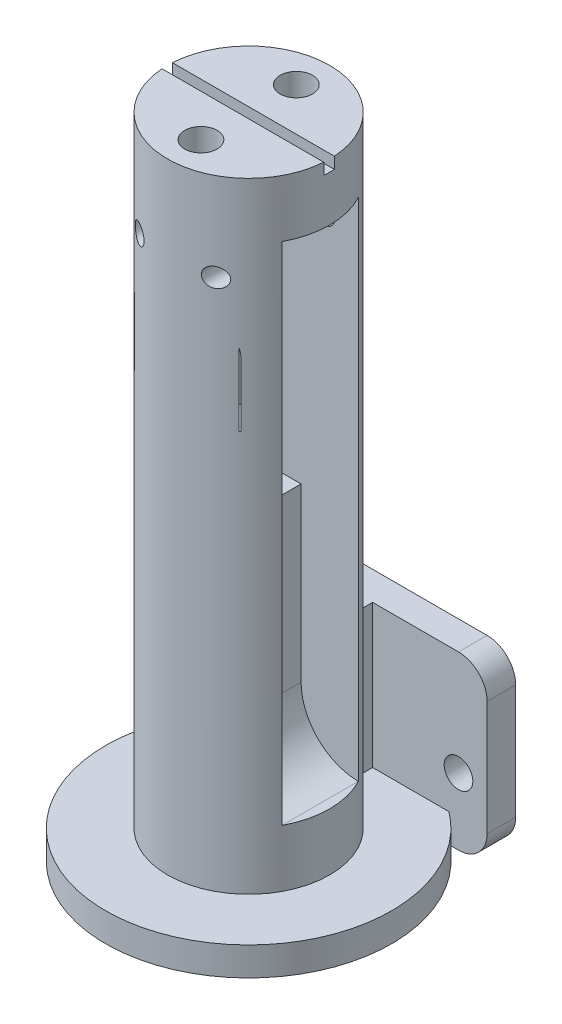
SolidWorks part; units mm, degrees
material "CA"
ref_plane "Alzado" through (0, 0, 0) normal (0, 0, 1) x (1, 0, 0)
ref_plane "Planta" through (0, 0, 0) normal (0, 1, 0) x (1, 0, 0)
ref_plane "Vista lateral" through (0, 0, 0) normal (1, 0, 0) x (0, 0, -1)
sketch "Croquis1" plane through (0, 0, 0) normal (0, 1, 0) x (1, 0, 0)
  circle A0 centre (0, 0) radius 15
  dimension "D1" = 30
extrude "Saliente-Extruir1" add sketch "Croquis1" along normal blind 3
sketch "Croquis2" plane through (0, 3, 0) normal (0, 1, 0) x (1, 0, 0)
  circle A0 centre (0, 0) radius 8.5
  dimension "D1" = 17
extrude "Saliente-Extruir2" add sketch "Croquis2" along normal blind 65
sketch "Croquis3" plane through (0, 0, 0) normal (0, 0, 1) x (1, 0, 0)
  line L0 (8.5, 3) -> (-8.5, 3) construction
  line L1 (-8.5, 62) -> (8.5, 62)
  line L2 (-8.5, 62) -> (-8.5, 9)
  line L3 (-8.5, 9) -> (8.5, 9)
  line L4 (8.5, 62) -> (8.5, 9)
  line L5 (-8.5, 62) -> (8.5, 9) construction
  line L6 (-8.5, 9) -> (8.5, 62) construction
  line L7 (7.5, 68) -> (-7.5, 68) construction
  point P0 (0, 35.5)
  dimension "D1" = 6
  dimension "D2" = 6
  dimension "D3" = 17
  dimension "D4" = 0
extrude "Cortar-Extruir1" cut sketch "Croquis3" against normal blind 4 and the other way blind 4 contours L2 L1 L4 L3
sketch "Croquis4" plane through (0, 0, 0) normal (0, 0, 1) x (1, 0, 0)
  line L0 (7.5, 68) -> (-7.5, 68) construction
  line L1 (0, 68) -> (0, 44.0462) construction
  circle A0 centre (-4, 58.75) radius 1
  circle A1 centre (4, 58.75) radius 1
  dimension "D1" = 2
  dimension "D2" = 4
  dimension "D5" = 9.25
extrude "Cortar-Extruir2" cut sketch "Croquis4" against normal blind 8 and the other way blind 8
sketch "Sketch9" plane through (0, 0, 0) normal (0, 0, 1) x (1, 0, 0)
  line L1 (-15.5683, -0.9904) -> (15.9293, -0.9904)
  line L2 (-15.5683, -0.9904) -> (-15.5683, 65.5246)
  line L3 (-15.5683, 65.5246) -> (15.9293, 65.5246)
  line L4 (15.9293, -0.9904) -> (15.9293, 65.5246)
extrude "Cut-Extrude7" [suppressed] cut sketch "Sketch9" against normal blind 30
sketch "Sketch10" [suppressed] plane through (0, 0, 3) normal (0, 0, -1) x (-1, 0, 0)
  line L0 (0, 63) -> (0, 0) construction
  line L2 (-5.6, 48.5) -> (-5.6, 42)
  line L3 (-5.6, 42) -> (5.6, 42)
  line L4 (5.6, 48.5) -> (5.6, 42)
  line L5 (-7.5, 63) -> (7.5, 63) construction
  line L6 (7.953, 57) -> (-7.953, 57) construction
  arc A3 (-5.6, 48.5) -> (5.6, 48.5) centre (0, 48.5) cw
  dimension "D3" = 15
  dimension "D4" = 5.6
  dimension "D1" = 11.2
  dimension "D2" = 6.5
sketch "Sketch11" plane through (0, 0, 4) normal (0, 0, -1) x (-1, 0, 0)
  line L0 (0, 68) -> (0, 27.3944) construction
  line L1 (5.6, 51.5) -> (5.6, 45)
  line L2 (5.6, 45) -> (-5.6, 45)
  line L3 (-5.6, 51.5) -> (-5.6, 45)
  line L4 (7.5, 68) -> (-7.5, 68) construction
  line L5 (-8.5, 62) -> (-7.5, 62) construction
  arc A1 (-5.6, 51.5) -> (5.6, 51.5) centre (0, 51.5) cw
  dimension "D2" = 5.6
  dimension "D1" = 11.2
  dimension "D3" = 17
  dimension "D4" = 6.5
extrude "Cut-Extrude9" cut sketch "Sketch11" against normal blind 2.5
sketch "Croquis5" plane through (0, 0, 0) normal (0, 0, 1) x (1, 0, 0)
  line L0 (-1, 3) -> (1, 3)
  line L1 (15, 3) -> (-15, 3) construction
  line L2 (1, 3) -> (1, 18)
  line L3 (1, 18) -> (-1, 18)
  line L4 (-1, 18) -> (-1, 3)
  point P5 (0, 3)
  dimension "D1" = 2
  dimension "D2" = 0
  dimension "D3" = 15
extrude "Saliente-Extruir3" add sketch "Croquis5" against normal blind 15
sketch "Croquis6" plane through (0, 0, -15) normal (0, 0, -1) x (-1, 0, 0)
  line L1 (-10, 0) -> (10, 0)
  line L2 (-13, 3) -> (-13, 15)
  line L3 (-10, 18) -> (10, 18)
  line L4 (13, 3) -> (13, 15)
  line L5 (-13, 0) -> (13, 18) construction
  line L6 (-13, 18) -> (13, 0) construction
  arc A0 (10, 18) -> (13, 15) centre (10, 15) cw
  arc A1 (10, 0) -> (13, 3) centre (10, 3) ccw
  arc A2 (-10, 0) -> (-13, 3) centre (-10, 3) cw
  arc A3 (-13, 15) -> (-10, 18) centre (-10, 15) cw
  circle A4 centre (-10, 7) radius 1.5
  circle A5 centre (10, 7) radius 1.5
  point P0 (0, 9)
  dimension "D4" = 3
  dimension "D5" = 3
  dimension "D6" = 3
  dimension "D1" = 18
  dimension "D2" = 26
  dimension "D3" = 0
  dimension "D7" = 7
  dimension "D8" = 7
  dimension "D9" = 3
  dimension "D10" = 3
  dimension "D11" = 9
extrude "Saliente-Extruir4" add sketch "Croquis6" against normal blind 3
sketch "Croquis7" plane through (0, 0, 0) normal (1, 0, 0) x (0, 0, -1)
  line L0 (12, 3) -> (-15, 3) construction
  line L1 (0, 9) -> (4, 9)
  line L4 (4, 9) -> (4, 33)
  line L5 (0, 9) -> (-4, 9)
  line L6 (-4, 9) -> (-4, 33)
  line L7 (4, 62) -> (4, 9) construction
  line L12 (-4, 62) -> (-4, 9) construction
  line L15 (0, 9) -> (0, 18) construction
  line L16 (4, 33) -> (-4, 33)
  line L24 (0, 33) -> (0, 9) construction
  line L27 (0, 33) -> (4, 9) construction
  point P0 (-1, 33)
  point P8 (0, 36)
  dimension "D1" = 6
extrude "Saliente-Extruir5" add sketch "Croquis7" along normal blind 1.5 and the other way blind 1.5
fillet "Redondeo2" radius 6 2 edges at (-1.5, 9, 0) (1.5, 9, 0)
sketch "Croquis8" plane through (0, 0, 0) normal (0, -1, 0) x (1, 0, 0)
  circle A0 centre (0, 0) radius 3
  dimension "D1" = 6
extrude "Cortar-Extruir3" cut sketch "Croquis8" against normal blind 10
sketch "Sketch1" plane through (-1.5, 0, 0) normal (-1, 0, 0) x (0, 0, 1)
  line L0 (0, 9) -> (0, 62) construction
  line L1 (-2.5, 23) -> (2.5, 23)
  line L2 (-2.5, 23) -> (-2.5, 18)
  line L3 (-2.5, 18) -> (2.5, 18)
  line L4 (2.5, 23) -> (2.5, 18)
  line L5 (-4, 62) -> (4, 62) construction
  line L6 (-4, 15) -> (4, 15) construction
  point P9 (0, 23)
  dimension "D1" = 5
  dimension "D2" = 5
  dimension "D3" = 8
extrude "Cut-Extrude1" cut sketch "Sketch1" against normal blind 1
sketch "Sketch2" plane through (-0.5, 0, 0) normal (-1, 0, 0) x (0, 0, 1)
  line L0 (0, 23) -> (0, 18) construction
  line L1 (2.5, 23) -> (-2.5, 23) construction
  line L2 (-2.5, 18) -> (2.5, 18) construction
  line L3 (0, 18) -> (-2.5, 20.5) construction
  line L4 (-2.5, 23) -> (-2.5, 18) construction
  line L5 (-2.5, 20.5) -> (2.5, 20.5) construction
  line L6 (2.5, 18) -> (2.5, 23) construction
  circle A0 centre (0, 20.5) radius 1.25
  dimension "D1" = 2.5
extrude "Cut-Extrude2" cut sketch "Sketch2" against normal blind 3
sketch "Sketch12" plane through (0, 68, 0) normal (0, 1, 0) x (1, 0, 0)
  line L8 (0, 0.5) -> (-8.4853, 0.5)
  line L9 (0, -0.6) -> (-8.4788, -0.6)
  line L10 (0, 0.5) -> (8.4853, 0.5)
  line L11 (0, -0.6) -> (8.4788, -0.6)
  arc A6 (-1, 8.441) -> (1, 8.441) centre (0, 0) ccw construction
  circle A7 centre (0, 0) radius 8.5 construction
  arc A8 (-8.4853, 0.5) -> (-8.4788, -0.6) centre (0, 0) ccw
  arc A9 (8.4788, -0.6) -> (8.4853, 0.5) centre (0, 0) ccw
  point P4 (0, 0)
extrude "Cut-Extrude10" cut sketch "Sketch12" against normal blind 1.2
hole_wizard "M3 Clearance Hole1" positions "Sketch17" profile "Sketch18" hole size "M3" standard "ANSI Metric"
sketch "Sketch17" plane through (0, 68, 0) normal (0, 1, 0) x (1, 0, 0)
  point P0 (0, 5)
  point P3 (0, -5)
  point P8 (0, 0)
  point P9 (0, 0)
sketch "Sketch18" plane through (0, 68, -5) normal (1, 0, 0) x (0, 0, 1)
  line L0 (0, 0) -> (0, 5)
  line L1 (0, 5) -> (1.7, 3.9785)
  line L2 (1.7, 3.9785) -> (1.7, 0)
  line L5 (1.7, 0) -> (0, 0)
  line L10 (0, 5) -> (-1.7, 3.9785) construction
  line L11 (0, -6.35) -> (0, 107.95) construction
  dimension "Hole Dia." = 3.4
  dimension "Hole Depth" = 5
  dimension "Drill Angle" = 118
